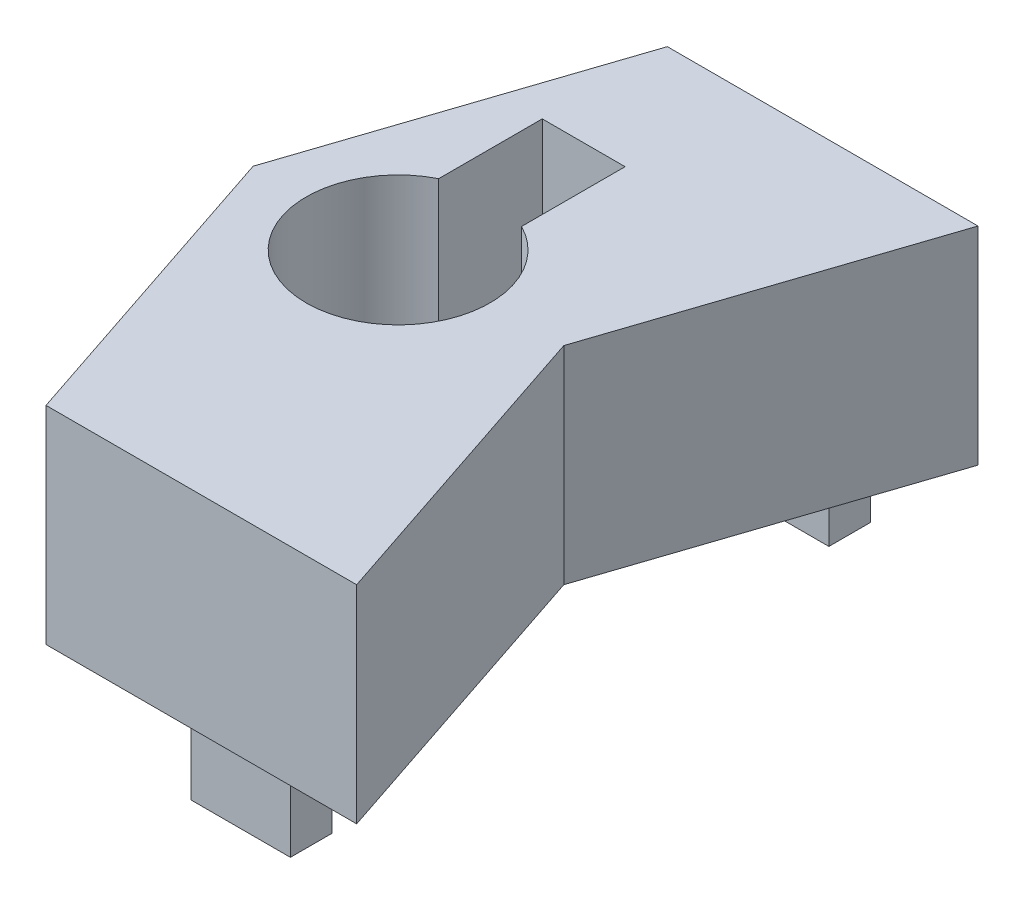
SolidWorks part; units mm, degrees
ref_plane "Front Plane" through (0, 0, 0) normal (0, 0, 1) x (1, 0, 0)
ref_plane "Top Plane" through (0, 0, 0) normal (0, 1, 0) x (1, 0, 0)
ref_plane "Right Plane" through (0, 0, 0) normal (1, 0, 0) x (0, 0, -1)
sketch "Sketch1" plane through (0, 0, 0) normal (0, 1, 0) x (1, 0, 0)
  line L0 (0, 0) -> (19.05, 0)
  line L1 (19.05, 0) -> (12.7, 19.05)
  line L2 (12.7, 19.05) -> (19.05, 38.1)
  line L3 (19.05, 38.1) -> (0, 38.1)
  line L4 (0, 38.1) -> (-6.35, 19.05)
  line L5 (-6.35, 19.05) -> (0, 0)
  dimension "D1" = 19.05
  dimension "D2" = 38.1
  dimension "D5" = 19.05
  dimension "D3" = 6.35
extrude "Boss-Extrude1" add sketch "Sketch1" along normal blind 12.7
sketch "Sketch2" plane through (0, 12.7, 0) normal (0, -1, 0) x (1, 0, 0)
  line L0 (12.7, -19.05) -> (-6.35, -19.05) construction
  line L1 (-6.35, -19.05) -> (0, 0) construction
  circle A0 centre (2.54, -19.05) radius 5.635
  dimension "D1" = 11.27
  dimension "D2" = 8.89
extrude "Haptic Motor Cutout" cut sketch "Sketch2" along normal blind 9.558 contours A0
sketch "Sketch3" plane through (0, 0, 0) normal (0, -1, 0) x (1, 0, 0)
  line L8 (5.08, -24.0801) -> (0, -24.0801)
  line L9 (5.08, -24.0801) -> (5.08, -30.4301)
  line L10 (0, -24.0801) -> (0, -30.4301)
  line L11 (5.08, -30.4301) -> (0, -30.4301)
  circle A3 centre (2.54, -19.05) radius 5.635 construction
  dimension "D1" = 5.08
  dimension "D2" = 6.35
extrude "Haptic Wire Cutout" cut sketch "Sketch3" against normal through all
ref_plane "MidPlane" through (0, 0, -19.05) normal (0, 0, -1) x (-1, 0, 0)
sketch "Sketch4" plane through (0, 0, 0) normal (0, -1, 0) x (1, 0, 0)
  line L0 (19.05, -38.1) -> (0, -38.1) construction
  line L1 (13.716, -36.83) -> (7.62, -36.83)
  line L2 (13.716, -36.83) -> (13.716, -34.29)
  line L3 (13.716, -34.29) -> (7.62, -34.29)
  line L4 (7.62, -36.83) -> (7.62, -34.29)
  line L5 (0, -55) -> (0, 55) construction
  dimension "D1" = 2.54
  dimension "D2" = 6.096
  dimension "D3" = 1.27
  dimension "D4" = 7.62
extrude "Pins" add sketch "Sketch4" along normal blind 5.08
mirror "Mirror1" about plane through (0, 0, -19.05) normal (0, 0, -1) of "Pins"
ref_point "Point1" [suppressed]
ref_axis "Axis1" [suppressed] through (0, 12.7, -38.1) along (0, 0, 1)
sketch "Sketch5" [suppressed] plane through (0, 12.7, 0) normal (0, 1, 0) x (1, 0, 0)
  line L0 (0, 38.1) -> (0, 0) construction
  line L1 (0, 19.05) -> (25.4, 19.05) construction
equation "\"Arrow Height\"= 1.5in"
equation "\"Button Height\"= 2in"
equation "\"Button Width\"= 4in"
equation "\"Haptic Diameter\"= 10mm"
equation "\"Haptic Thickness\"= 2.7mm"
equation "\"D2@Sketch1\"=\"Arrow Height\""
equation "\"D5@Sketch1\"=\"Arrow Height\"/2"
equation "\"D1@Sketch2\"=\"Haptic Diameter\"+.05in"
equation "\"D1@Haptic Motor Cutout\"=\"Haptic Thickness\" + .02+.25"
equation "\"D1\"= \"Haptic Thickness\" + .02 + .25"
equation "\"Arrow Spacing\"= 1in"
equation "\"Arrow Width\"= 01in"
equation "\"Haptic Wire Angle\"= 63.43"
equation "\"Haptic Wire Width\"= .1in"
equation "\"Haptic Wire Height\"= .15in"
